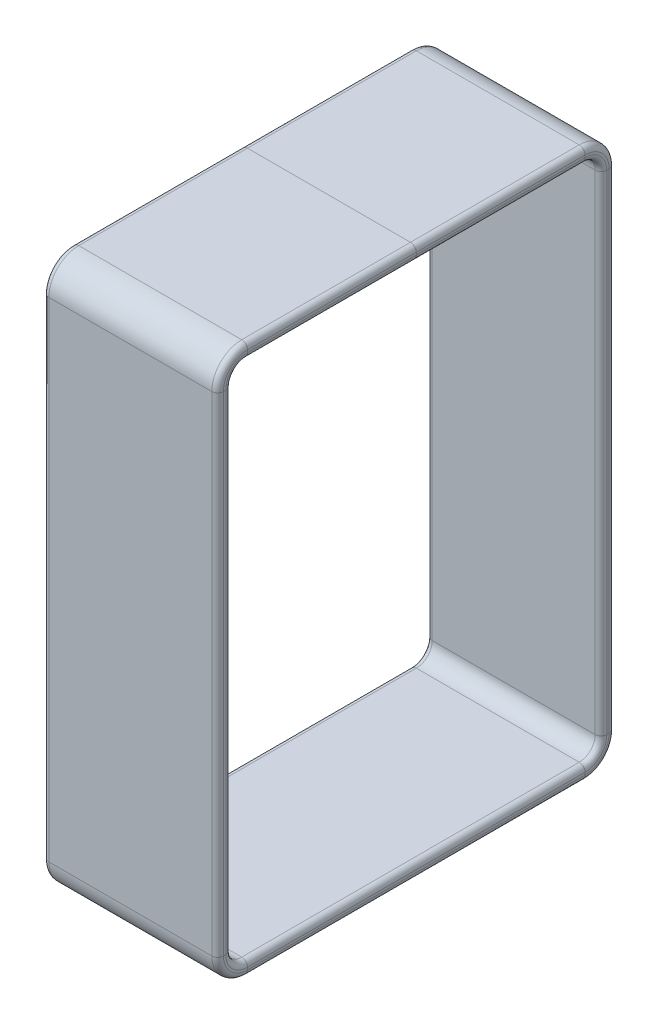
SolidWorks part; units mm, degrees
ref_plane "Front Plane" through (0, 0, 0) normal (0, 0, 1) x (1, 0, 0)
ref_plane "Top Plane" through (0, 0, 0) normal (0, 1, 0) x (1, 0, 0)
ref_plane "Right Plane" through (0, 0, 0) normal (1, 0, 0) x (0, 0, -1)
sketch "Sketch1" plane through (0, 0, 0) normal (1, 0, 0) x (0, 0, -1)
  line L1 (14.5, 23) -> (-14.5, 23)
  line L2 (16.5, 21) -> (16.5, -21)
  line L3 (14.5, -23) -> (-14.5, -23)
  line L4 (-16.5, 21) -> (-16.5, -21)
  line L5 (16.5, 23) -> (-16.5, -23) construction
  line L6 (16.5, -23) -> (-16.5, 23) construction
  arc A0 (-14.5, -23) -> (-16.5, -21) centre (-14.5, -21) cw
  arc A1 (16.5, -21) -> (14.5, -23) centre (14.5, -21) cw
  arc A2 (14.5, 23) -> (16.5, 21) centre (14.5, 21) cw
  arc A3 (-14.5, 23) -> (-16.5, 21) centre (-14.5, 21) ccw
  point P0 (0, 0)
  dimension "D3" = 2
  dimension "D1" = 46
  dimension "D2" = 33
sketch "Sketch2" plane through (0, 0, 0) normal (0, 0, 1) x (1, 0, 0)
  line L0 (0, -23) -> (0, 23) construction
  line L1 (-7, 23.5688) -> (7, 23.5688)
  line L2 (-7.5, 23.0688) -> (-7.5, 22.8688)
  line L3 (-7, 22.3688) -> (7, 22.3688)
  line L4 (7.5, 23.0688) -> (7.5, 22.8688)
  line L5 (-7.5, 23.5688) -> (7.5, 22.3688) construction
  line L6 (-7.5, 22.3688) -> (7.5, 23.5688) construction
  line L7 (0, 23) -> (0, -23) construction
  arc A0 (7, 22.3688) -> (7.5, 22.8688) centre (7, 22.8688) ccw
  arc A1 (7, 23.5688) -> (7.5, 23.0688) centre (7, 23.0688) cw
  arc A2 (-7.5, 22.8688) -> (-7, 22.3688) centre (-7, 22.8688) ccw
  arc A3 (-7, 23.5688) -> (-7.5, 23.0688) centre (-7, 23.0688) ccw
  point P0 (0, 22.9688)
  point P7 (0, 0)
  dimension "D3" = 0.5
  dimension "D1" = 15
  dimension "D2" = 1.2
sweep "Sweep1" add profiles "Sketch2" path "Sketch1"
